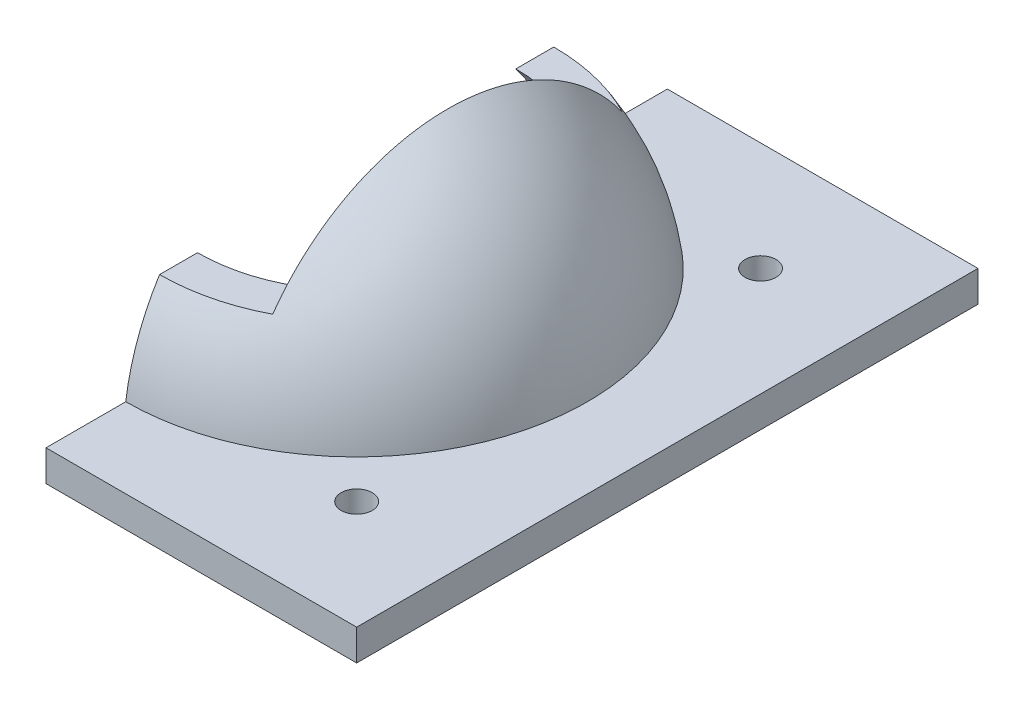
SolidWorks part; units mm, degrees
ref_plane "Front Plane" through (0, 0, 0) normal (0, 0, 1) x (1, 0, 0)
ref_plane "Top Plane" through (0, 0, 0) normal (0, 1, 0) x (1, 0, 0)
ref_plane "Right Plane" through (0, 0, 0) normal (1, 0, 0) x (0, 0, -1)
sketch "Sketch1" plane through (0, 0, 0) normal (0, 0, 1) x (1, 0, 0)
  line L0 (16.51, 0) -> (19.05, 0) construction
  line L1 (19.05, 0) -> (16.51, 0) construction
  line L2 (19.05, 0) -> (16.51, 0)
  line L3 (0, 19.05) -> (0, 16.51)
  arc A0 (19.05, 0) -> (0, 19.05) centre (0, 0) ccw
  arc A2 (16.51, 0) -> (0, 16.51) centre (0, 0) ccw
  circle A3 centre (0, 0) radius 19.05 construction
  circle A4 centre (0, 0) radius 16.51 construction
  dimension "D1" = 38.1
  dimension "D2" = 2.54
revolve "Revolve1" add sketch "Sketch1" angle 360 about L3
sketch "Sketch2" plane through (0, 0, 0) normal (0, 0, 1) x (1, 0, 0)
  line L0 (0, 10.16) -> (0, 0) construction
  line L1 (-7.4295, 22.7688) -> (7.4295, 22.7688)
  line L2 (-7.4295, 22.7688) -> (-7.4295, 10.16)
  line L3 (-7.4295, 10.16) -> (7.4295, 10.16)
  line L4 (7.4295, 22.7688) -> (7.4295, 10.16)
  dimension "D1" = 10.16
  dimension "D2" = 14.859
extrude "Cut-Extrude1" cut sketch "Sketch2" against normal mid plane 127
sketch "Sketch3" plane through (0, 0, 0) normal (0, -1, 0) x (1, 0, 0)
  line L1 (25.4, -25.4) -> (-25.4, -25.4)
  line L2 (25.4, -25.4) -> (25.4, 25.4)
  line L3 (25.4, 25.4) -> (-25.4, 25.4)
  line L4 (-25.4, -25.4) -> (-25.4, 25.4)
  line L5 (25.4, -25.4) -> (-25.4, 25.4) construction
  line L6 (25.4, 25.4) -> (-25.4, -25.4) construction
  circle A0 centre (0, 0) radius 16.51
  point P0 (0, 0)
  dimension "D2" = 33.02
  dimension "D1" = 50.8
sketch "Sketch4" plane through (0, 0, 0) normal (0, -1, 0) x (1, 0, 0)
  line L0 (25.4, -25.4) -> (-25.4, 25.4) construction
  circle A0 centre (0.1236, -0.1236) radius 16.51
  dimension "D1" = 33.02
extrude "Boss-Extrude1" add sketch "Sketch3" against normal blind 2.54
sketch "Sketch5" plane through (0, 2.54, 0) normal (0, 1, 0) x (1, 0, 0)
  line L0 (-16.51, 25.4) -> (-16.51, 16.51) construction
  line L1 (-25.4, 25.4) -> (25.4, 25.4) construction
  line L2 (-16.51, 16.51) -> (-25.4, 16.51) construction
  line L3 (-25.4, -25.4) -> (-25.4, 25.4) construction
  circle A0 centre (-16.51, 16.51) radius 1.27
  dimension "D2" = 2.54
  dimension "D1" = 8.89
extrude "Cut-Extrude3" cut sketch "Sketch5" against normal through all contours A0
pattern_linear "LPattern1" count 2 spacing 33.02 along (1, 0, 0) count 2 spacing 33.02 along (0, 0, 1) of "Cut-Extrude3"
sketch "Sketch7" plane through (-25.4, 0, 0) normal (-1, 0, 0) x (0, 0, 1)
  line L1 (27.5805, -2.6409) -> (-28.3451, -2.6409)
  line L2 (27.5805, -2.6409) -> (27.5805, 22.1646)
  line L3 (27.5805, 22.1646) -> (-28.3451, 22.1646)
  line L4 (-28.3451, -2.6409) -> (-28.3451, 22.1646)
extrude "Cut-Extrude4" cut sketch "Sketch7" against normal blind 25.4
